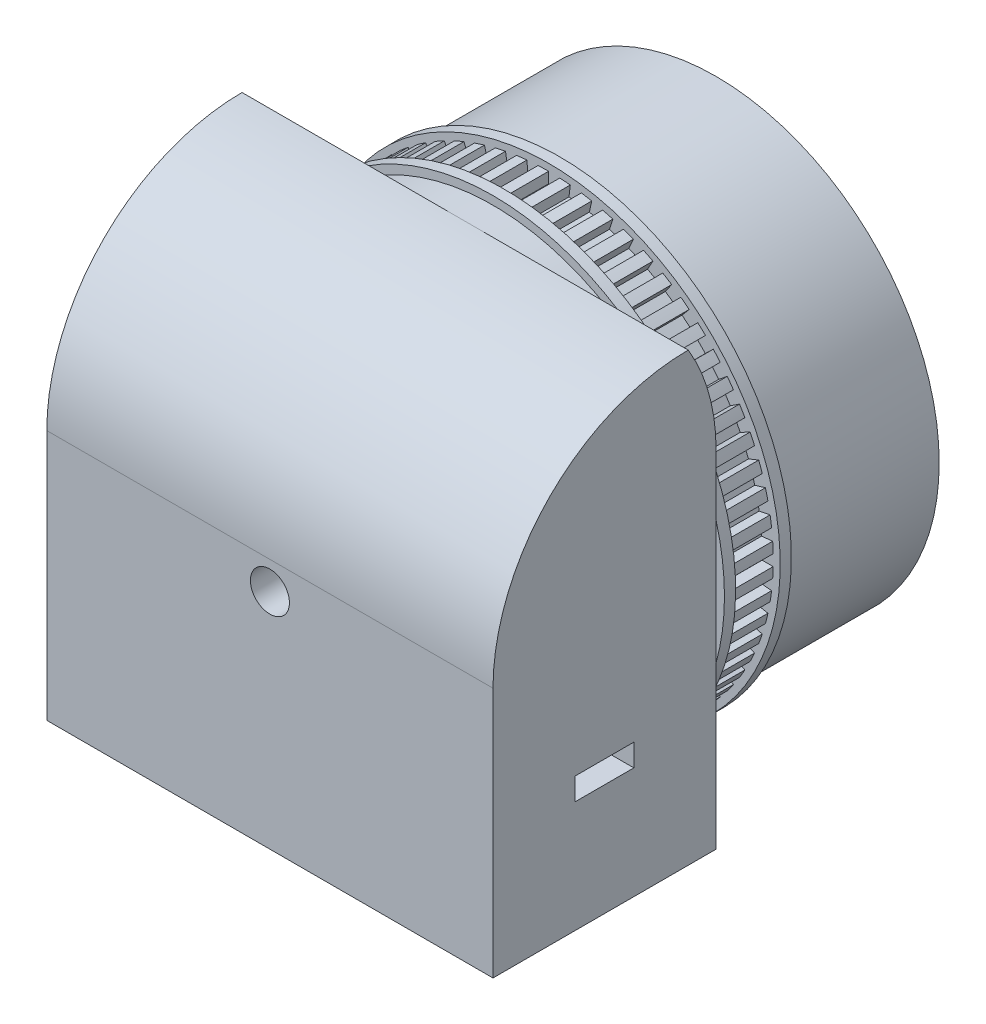
SolidWorks part; units mm, degrees
ref_plane "Front Plane" through (0, 0, 0) normal (0, 0, 1) x (1, 0, 0)
ref_plane "Top Plane" through (0, 0, 0) normal (0, 1, 0) x (1, 0, 0)
ref_plane "Right Plane" through (0, 0, 0) normal (1, 0, 0) x (0, 0, -1)
sketch "Sketch2" plane through (0, 0, 0) normal (0, 0, 1) x (1, 0, 0)
  circle A0 centre (0, 0) radius 40
  dimension "D1" = 80
extrude "Boss-Extrude1" add sketch "Sketch2" along normal blind 40
sketch "Sketch3" plane through (0, 0, 40) normal (0, 0, 1) x (1, 0, 0)
  line L1 (-40, 40) -> (40, 40)
  line L2 (-40, 40) -> (-40, -40)
  line L3 (-40, -40) -> (40, -40)
  line L4 (40, 40) -> (40, -40)
  line L5 (-40, 40) -> (40, -40) construction
  line L6 (-40, -40) -> (40, 40) construction
  point P0 (0, 0)
  dimension "D1" = 80
  dimension "D2" = 80
extrude "Boss-Extrude2" add sketch "Sketch3" along normal blind 40
fillet "Fillet1" radius 35 1 edges at (0, 40, 80)
fillet "Fillet2" radius 35 2 edges at (20, 40, 40) (-20, 40, 40)
sketch "Sketch4" plane through (0, -40, 0) normal (0, -1, 0) x (1, 0, 0)
  line L0 (-40, 80) -> (40, 40) construction
  line L2 (-20.4, 69.9) -> (20.4, 69.9)
  line L3 (-20.4, 69.9) -> (-20.4, 50.1)
  line L4 (-20.4, 50.1) -> (20.4, 50.1)
  line L5 (20.4, 69.9) -> (20.4, 50.1)
  line L6 (-20.4, 69.9) -> (20.4, 50.1) construction
  line L7 (-20.4, 50.1) -> (20.4, 69.9) construction
  point P4 (0, 60)
  dimension "D1" = 40.8
  dimension "D2" = 19.8
extrude "Cut-Extrude1" cut sketch "Sketch4" against normal blind 43
sketch "Sketch5" plane through (0, -40, 0) normal (0, -1, 0) x (1, 0, 0)
  line L0 (-40, 80) -> (-40, 40) construction
  line L1 (-40, 69.8633) -> (40, 69.8633)
  line L2 (-40, 69.8633) -> (-40, 50.0633)
  line L3 (-40, 50.0633) -> (40, 50.0633)
  line L4 (40, 69.8633) -> (40, 50.0633)
  line L5 (40, 80) -> (40, 40) construction
  line L6 (-20.4, 59.9817) -> (-25.4, 59.9817)
  line L7 (-20.4, 69.9) -> (-25.4, 69.9)
  line L8 (-20.4, 69.9) -> (-20.4, 50.0633)
  line L9 (-20.4, 50.0633) -> (-25.4, 50.0633)
  line L10 (-25.4, 69.9) -> (-25.4, 50.0633)
  line L11 (-25.4, 59.9817) -> (-20.4, 50.0633)
  line L12 (-25.4, 59.9817) -> (-20.4, 69.9)
  line L13 (20.4, 59.9817) -> (25.4, 59.9817)
  line L14 (20.4, 69.9) -> (25.4, 69.9)
  line L15 (20.4, 69.9) -> (20.4, 50.0633)
  line L16 (20.4, 50.0633) -> (25.4, 50.0633)
  line L17 (25.4, 69.9) -> (25.4, 50.0633)
  line L18 (25.4, 59.9817) -> (20.4, 50.0633)
  line L19 (25.4, 59.9817) -> (20.4, 69.9)
  circle A0 centre (-22.9, 64.9408) radius 1
  circle A1 centre (-22.9, 55.0225) radius 1
  circle A2 centre (22.9, 64.9408) radius 1
  circle A3 centre (22.9, 55.0225) radius 1
  dimension "D3" = 2
  dimension "D5" = 2
  dimension "D1" = 19.8
  dimension "D2" = 5
  dimension "D4" = 5
extrude "Cut-Extrude3" cut sketch "Sketch5" against normal blind 10 contours A0 | A1 | A2 | A3
sketch "Sketch6" plane through (0, 0, 0) normal (0, 0, -1) x (-1, 0, 0)
  line L1 (-2, 20) -> (2, 20)
  line L2 (-4, 18) -> (-4, -18)
  line L3 (-2, -20) -> (2, -20)
  line L4 (4, 18) -> (4, -18)
  line L5 (-4, 20) -> (4, -20) construction
  line L6 (-4, -20) -> (4, 20) construction
  line L7 (-18, 4) -> (18, 4)
  line L8 (-20, 2) -> (-20, -2)
  line L9 (-18, -4) -> (18, -4)
  line L10 (20, 2) -> (20, -2)
  line L11 (-20, 4) -> (20, -4) construction
  line L12 (-20, -4) -> (20, 4) construction
  arc A0 (2, -20) -> (4, -18) centre (2, -18) ccw
  arc A1 (-2, -20) -> (-4, -18) centre (-2, -18) cw
  arc A2 (2, 20) -> (4, 18) centre (2, 18) cw
  arc A3 (-4, 18) -> (-2, 20) centre (-2, 18) cw
  arc A4 (20, -2) -> (18, -4) centre (18, -2) cw
  arc A5 (20, 2) -> (18, 4) centre (18, 2) ccw
  arc A6 (-20, -2) -> (-18, -4) centre (-18, -2) ccw
  arc A7 (-20, 2) -> (-18, 4) centre (-18, 2) cw
  point P0 (0, 0)
  point P18 (0, 0)
  dimension "D3" = 2
  dimension "D6" = 2
  dimension "D1" = 8
  dimension "D2" = 40
  dimension "D4" = 8
  dimension "D5" = 40
extrude "Cut-Extrude4" cut sketch "Sketch6" against normal blind 2 contours A3 L2 L7 L4 A2 L1 | A7 L8 A6 L9 L2 L7 | L2 L9 L4 L7 | L10 A5 L7 L4 L9 A4 | A1 L3 A0 L4 L9 L2 region at (0, 11.8973, 0) region at (0, 0, 0) region at (11.8973, 0, 0) region at (-11.8973, 0, 0) region at (0, -11.8973, 0)
sketch "Sketch7" plane through (0, 0, 2) normal (0, 0, -1) x (-1, 0, 0)
  circle A0 centre (0, 0) radius 3.5
  dimension "D1" = 7
extrude "Cut-Extrude5" cut sketch "Sketch7" against normal through all
ref_plane "Plane1" through (0, 0, 40) normal (0, 0, -1) x (-1, 0, 0)
sketch "Sketch8" plane through (0, 0, 40) normal (0, 0, -1) x (-1, 0, 0)
  circle A0 centre (0, 0) radius 41.5
  dimension "D1" = 83
extrude "Boss-Extrude3" add sketch "Sketch8" along normal blind 2
sketch "Sketch9" plane through (0, 0, 40) normal (0, 0, -1) x (-1, 0, 0)
  circle A0 centre (0, 0) radius 40.25
  dimension "D1" = 80.5
extrude "Boss-Extrude4" add sketch "Sketch9" along normal blind 10
ref_plane "Plane2" through (0, 0, 30) normal (0, 0, -1) x (-1, 0, 0)
sketch "Sketch10" plane through (0, 0, 30) normal (0, 0, -1) x (-1, 0, 0)
  circle A0 centre (0, 0) radius 41.5
  dimension "D1" = 83
extrude "Boss-Extrude5" add sketch "Sketch10" along normal blind 2
sketch "Sketch11" plane through (0, 0, 30) normal (0, 0, -1) x (-1, 0, 0)
  line L0 (0, 0) -> (-40.25, 0) construction
  line L1 (-40.25, 1) -> (-40.25, -1)
  line L3 (-40.25, 1) -> (-38.25, 1)
  line L4 (-40.25, 1) -> (-40.25, -1)
  line L5 (-40.25, -1) -> (-38.25, -1)
  line L6 (-38.25, 1) -> (-38.25, -1)
  circle A0 centre (0, 0) radius 40.25 construction
  point P10 (-40.25, 0)
  dimension "D1" = 2
  dimension "D2" = 2
extrude "Cut-Extrude14" cut sketch "Sketch11" against normal blind 8 contours L0 L6 L3 L1 | L6 L0 L4 L5 region at (39.25, -0.5, 30) region at (39.25, 0.5, 30)
pattern_circular "CirPattern4" count 65 over 360 about axis through (0, 0, 30) along (0, 0, 1) of "Cut-Extrude14" reverse direction yes
sketch "Sketch12" plane through (-40, 0, 0) normal (-1, 0, 0) x (0, 0, 1)
  line L0 (40, 44) -> (40, -44) construction
  line L1 (80, -40) -> (40, -40)
  line L2 (80, -40) -> (80, -20)
  line L3 (80, -20) -> (40, -20)
  line L4 (40, -40) -> (40, -20)
  line L6 (54.7463, -18) -> (65.2537, -18)
  line L7 (54.7463, -18) -> (54.7463, -22)
  line L8 (54.7463, -22) -> (65.2537, -22)
  line L9 (65.2537, -18) -> (65.2537, -22)
  line L10 (54.7463, -18) -> (65.2537, -22) construction
  line L11 (54.7463, -22) -> (65.2537, -18) construction
  line L12 (54.7463, -20) -> (65.2537, -20)
  line L13 (54.7463, -20) -> (54.7463, -16)
  line L14 (54.7463, -16) -> (65.2537, -16)
  line L15 (65.2537, -20) -> (65.2537, -16)
  point P7 (60, -20)
  dimension "D1" = 20
  dimension "D2" = 4
  dimension "D3" = 4
extrude "Cut-Extrude18" cut sketch "Sketch12" against normal through all contours L13 L14 L15 L12
